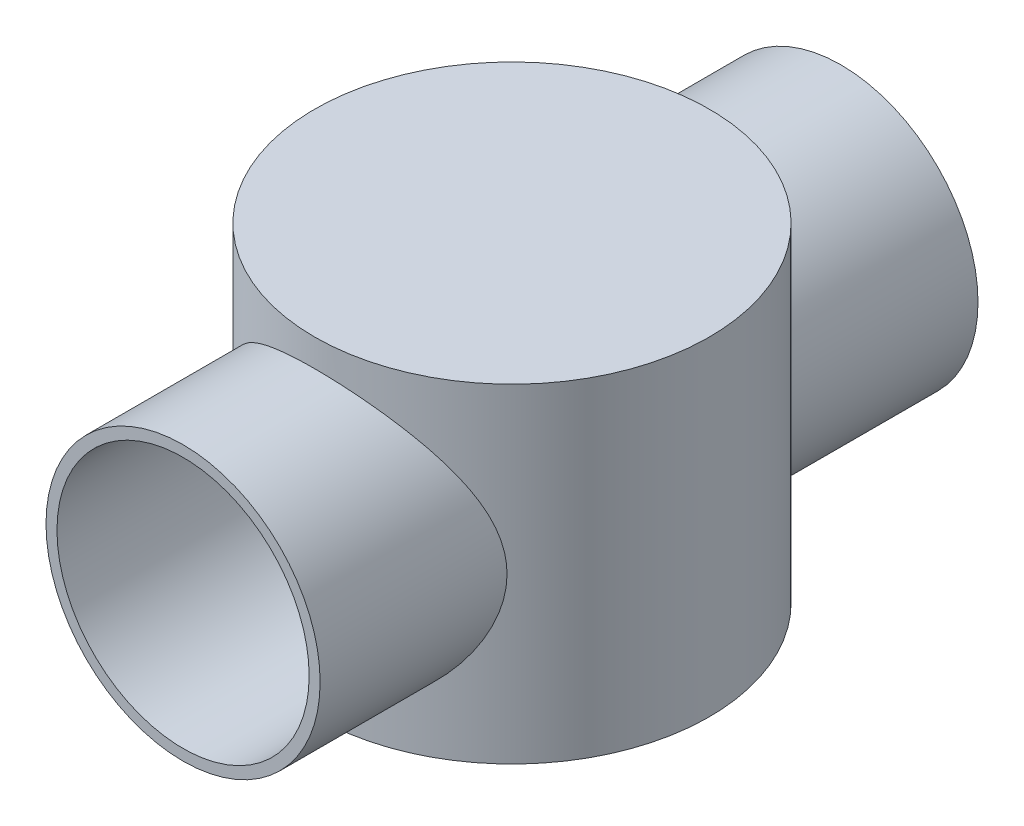
SolidWorks part; units mm, degrees
ref_plane "Front Plane" through (0, 0, 0) normal (0, 0, 1) x (1, 0, 0)
ref_plane "Top Plane" through (0, 0, 0) normal (0, 1, 0) x (1, 0, 0)
ref_plane "Right Plane" through (0, 0, 0) normal (1, 0, 0) x (0, 0, -1)
sketch "Sketch1" plane through (0, 0, 0) normal (0, 1, 0) x (1, 0, 0)
  circle A0 centre (0, 0) radius 18
  dimension "D1" = 36
extrude "Boss-Extrude1" add sketch "Sketch1" along normal blind 30
sketch "Sketch2" plane through (0, 0, 0) normal (0, 0, 1) x (1, 0, 0)
  line L2 (-18, 0) -> (18, 0) construction
  circle A0 centre (0, 15) radius 12.5
  point P2 (0, 0)
  dimension "D2" = 25
  dimension "D1" = 15
extrude "Boss-Extrude2" add sketch "Sketch2" along normal blind 30 and the other way blind 30
sketch "Sketch3" plane through (0, 0, 30) normal (0, 0, 1) x (1, 0, 0)
  circle A0 centre (0, 15) radius 11.5
extrude "Cut-Extrude1" cut sketch "Sketch3" against normal through all
